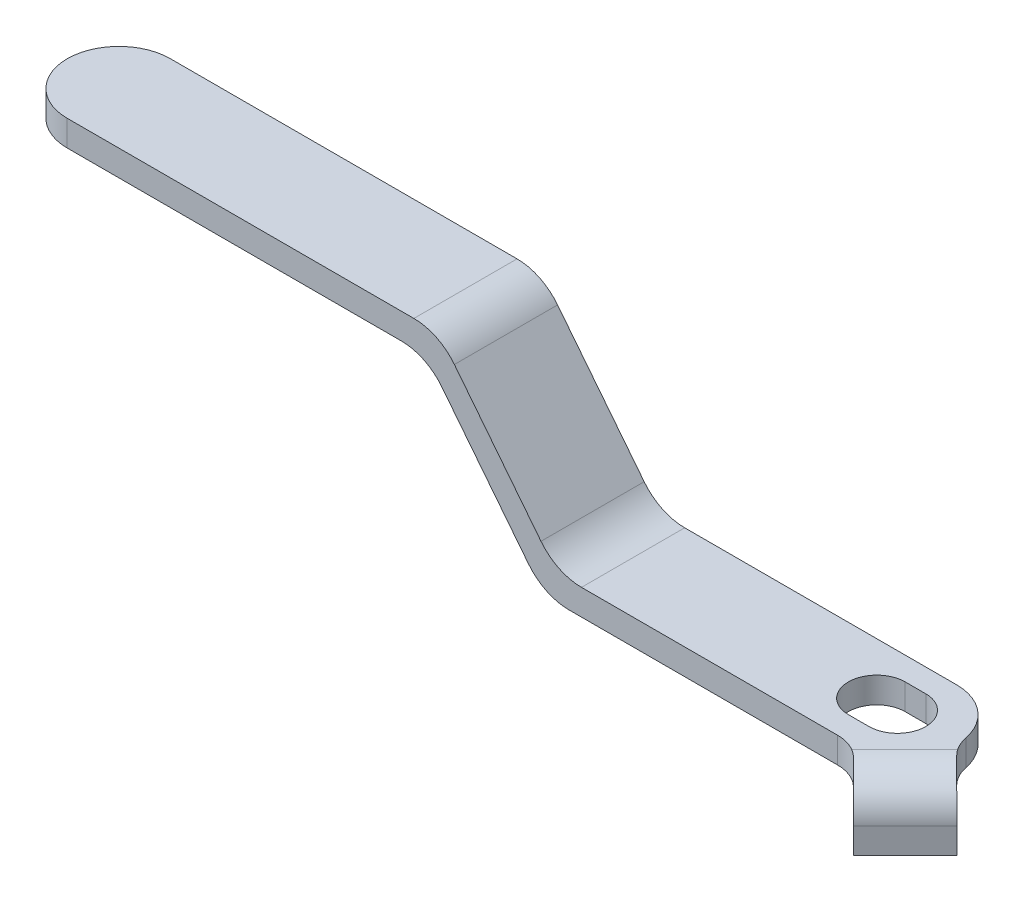
SolidWorks part; units mm, degrees
ref_plane "Przednia" through (0, 0, 0) normal (0, 0, 1) x (1, 0, 0)
ref_plane "Górna" through (0, 0, 0) normal (0, 1, 0) x (1, 0, 0)
ref_plane "Prawa" through (0, 0, 0) normal (1, 0, 0) x (0, 0, -1)
sketch "Szkic2" plane through (0, 0, 0) normal (0, 0, 1) x (1, 0, 0)
  line L0 (0, 0) -> (-70, 0)
  line L1 (-70, 0) -> (-92.7913, 28.9013)
  line L2 (-92.7913, 28.9013) -> (-172.41, 28.9013)
  dimension "D1" = 70
  dimension "D2" = 172.41
  dimension "D3" = 28.9013
extrude "Wyciągnięcie-cienka ścianka1" add sketch "Szkic2" along normal mid plane 20 thin contours L0 L1 L2 thin type one direction wall 5
fillet "Zaokrąglenie1" radius 10 4 edges at (-70, 0, 0) (-67.5753, 5, 0) (-92.7913, 28.9013, 0) (-90.3666, 33.9013, 0)
fillet "Zaokrąglenie2" radius 10 4 edges at (-172.41, 31.4013, -10) (-172.41, 31.4013, 10) (0, 2.5, -10) (0, 2.5, 10)
sketch "Szkic6" plane through (0, 5, 0) normal (0, 1, 0) x (1, 0, 0)
  line L0 (-10, 10) -> (-62.7259, 10) construction
  line L1 (-15.4911, 0) -> (-11.4911, 0) construction
  line L2 (-15.4911, 5.5) -> (-11.4911, 5.5)
  line L3 (-15.4911, -5.5) -> (-11.4911, -5.5)
  arc A0 (-15.4911, 5.5) -> (-15.4911, -5.5) centre (-15.4911, 0) ccw
  arc A1 (-11.4911, -5.5) -> (-11.4911, 5.5) centre (-11.4911, 0) ccw
  point P3 (-13.4911, 0)
  dimension "D1" = 11
  dimension "D2" = 4
  dimension "D3" = 4.5
extrude "Wytnij-wyciągnięcie1" cut sketch "Szkic6" against normal through all
sketch "Szkic9" plane through (0, 5, 0) normal (0, 1, 0) x (1, 0, 0)
  line L2 (-10, -10) -> (-62.7259, -10) construction
  line L4 (-10, -10) -> (-3.8399, -16.1601)
  line L5 (-3.8399, -16.1601) -> (6.1682, -6.1519)
  line L6 (6.1682, -6.1519) -> (0, 0)
  arc A0 (-10, -10) -> (0, 0) centre (-10, 0) ccw construction
  arc A1 (-10, -10) -> (0, 0) centre (-10, 0) ccw
extrude "Dodanie-wyciągnięcie7" add sketch "Szkic9" against normal blind 5
sketch "Szkic13" plane through (0, 0, 0) normal (0, -1, 0) x (1, 0, 0)
  line L0 (-3.8399, 16.1601) -> (-7.3755, 12.6245)
  line L1 (-10, 10) -> (-3.8399, 16.1601) construction
  line L2 (-7.3755, 12.6245) -> (2.6147, 2.6077)
  line L3 (6.1682, 6.1519) -> (0, 0) construction
  line L4 (2.6147, 2.6077) -> (6.1682, 6.1519)
  line L5 (6.1682, 6.1519) -> (-3.8399, 16.1601)
  dimension "D1" = 5
extrude "Dodanie-wyciągnięcie8" add sketch "Szkic13" along normal blind 7.5
fillet "Zaokrąglenie8" radius 7.5 1 edges at (-10, 2.5, 10)
fillet "Zaokrąglenie9" radius 7.5 1 edges at (0, 2.5, 0)
fillet "Zaokrąglenie10" radius 7.5 1 edges at (1.1642, 5, 11.156)
fillet "Zaokrąglenie12" radius 2 1 edges at (-2.3804, 0, 7.6161)
